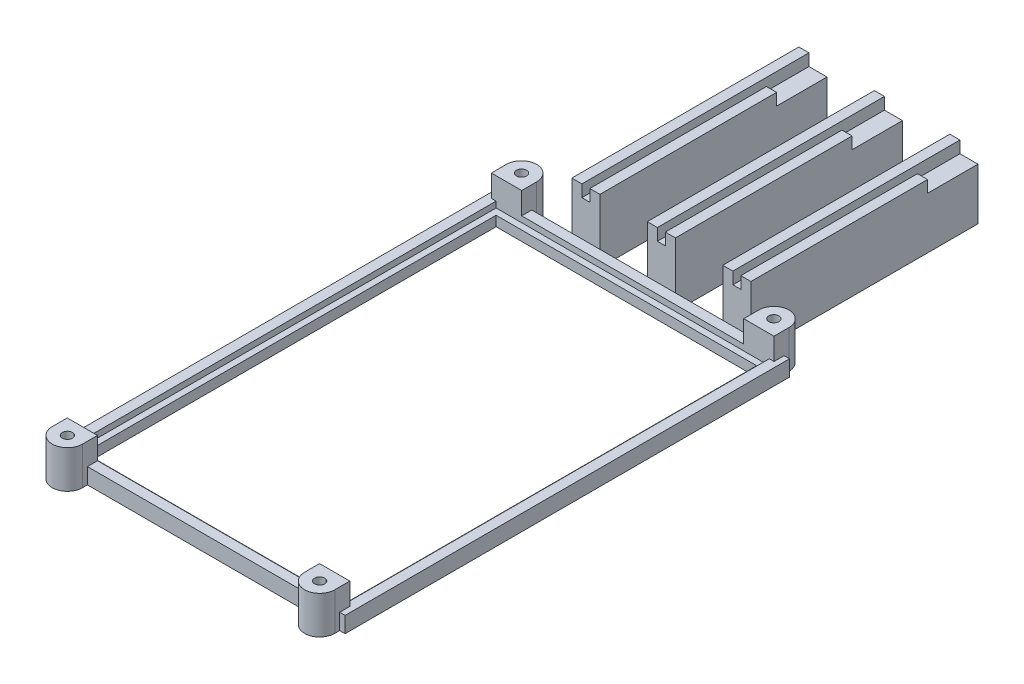
SolidWorks part; units mm, degrees
ref_plane "Front Plane" through (0, 0, 0) normal (0, 0, 1) x (1, 0, 0)
ref_plane "Top Plane" through (0, 0, 0) normal (0, 1, 0) x (1, 0, 0)
ref_plane "Right Plane" through (0, 0, 0) normal (1, 0, 0) x (0, 0, -1)
sketch "Sketch1" plane through (0, 0, 0) normal (0, 1, 0) x (1, 0, 0)
  line L1 (-34.375, -53.375) -> (34.375, -53.375)
  line L2 (-34.375, -53.375) -> (-34.375, 53.375)
  line L3 (-34.375, 53.375) -> (34.375, 53.375)
  line L4 (34.375, -53.375) -> (34.375, 53.375)
  line L5 (-34.375, -53.375) -> (34.375, 53.375) construction
  line L6 (-34.375, 53.375) -> (34.375, -53.375) construction
  point P0 (0, 0)
  dimension "D1" = 68.75
  dimension "D2" = 106.75
extrude "Extrude-Thin1" add sketch "Sketch1" along normal blind 4 thin thin type one direction wall 2.54
sketch "Sketch2" plane through (0, 0, 0) normal (0, 1, 0) x (1, 0, 0)
  line L0 (-34.375, 53.375) -> (0, 19) construction
  line L1 (0, 19) -> (34.375, 53.375) construction
  line L3 (32.7875, -51.7875) -> (-32.7875, -51.7875)
  line L4 (34.375, 53.375) -> (-34.375, 53.375)
  line L5 (34.375, -53.375) -> (34.375, 53.375)
  line L6 (-34.375, -53.375) -> (34.375, -53.375)
  line L7 (-34.375, 53.375) -> (-34.375, -53.375)
  line L8 (34.375, 53.375) -> (-34.375, 53.375)
  line L9 (34.375, -53.375) -> (34.375, 53.375)
  line L10 (-34.375, -53.375) -> (34.375, -53.375)
  line L11 (-34.375, 53.375) -> (-34.375, -53.375)
  line L12 (32.7875, -51.7875) -> (32.7875, 51.7875)
  line L13 (32.7875, 51.7875) -> (-32.7875, 51.7875)
  line L14 (-32.7875, -51.7875) -> (-32.7875, 51.7875)
  line L15 (32.7875, -51.7875) -> (-32.7875, 51.7875) construction
  line L16 (32.7875, 51.7875) -> (-32.7875, -51.7875) construction
  point P2 (0, 0)
  point P11 (-31.0567, 50.0567)
  dimension "D2" = 1.5875
  dimension "D1" = 0
extrude "Boss-Extrude2" add sketch "Sketch2" along normal offset from surface (2.5 mm away) 1.5 up to face at (0, 4, 0)
sketch "Sketch4" plane through (0, 0, -55.915) normal (0, 0, -1) x (-1, 0, 0)
  line L0 (34.375, 4) -> (17.865, 4) construction
  line L1 (-36.915, 4) -> (36.915, 4) construction
  line L2 (17.865, 0) -> (17.865, 16)
  line L3 (-36.915, 0) -> (36.915, 0) construction
  line L4 (17.865, 16) -> (15.325, 16)
  line L5 (15.325, 16) -> (15.325, 13)
  line L6 (15.325, 13) -> (13.325, 13)
  line L7 (13.325, 13) -> (13.325, 16)
  line L8 (13.325, 16) -> (10.785, 16)
  line L9 (10.785, 16) -> (10.785, 0)
  line L10 (10.785, 0) -> (17.865, 0)
  point P9 (22.6104, 16)
  dimension "D1" = 2
  dimension "D2" = 9
  dimension "D3" = 3
  dimension "D4" = 2.54
  dimension "D5" = 19.05
extrude "Boss-Extrude3" add sketch "Sketch4" along normal blind 57.15
sketch "Sketch5" plane through (0, 0, -113.065) normal (0, 0, -1) x (-1, 0, 0)
  line L1 (10.785, 16) -> (13.325, 16)
  line L2 (10.785, 16) -> (10.785, 13)
  line L3 (10.785, 13) -> (13.325, 13)
  line L4 (13.325, 16) -> (13.325, 13)
extrude "Cut-Extrude1" cut sketch "Sketch5" against normal offset from surface (12.7 mm away) 44.45 up to face at (-14.325, 12.25, -55.915)
pattern_linear "LPattern1" count 3 spacing 19 along (1, 0, 0) of "Cut-Extrude1", "Boss-Extrude3"
sketch "Sketch6" plane through (0, 0, 0) normal (0, 1, 0) x (1, 0, 0)
  line L0 (35.56, 57.15) -> (35.56, 53.375)
  line L1 (35.56, 53.375) -> (27.94, 53.375)
  line L2 (34.375, 53.375) -> (-34.375, 53.375) construction
  line L3 (27.94, 53.375) -> (27.94, 57.15)
  circle A0 centre (31.75, 57.15) radius 1.27
  arc A1 (35.56, 57.15) -> (27.94, 57.15) centre (31.75, 57.15) ccw
  dimension "D2" = 2.54
  dimension "D4" = 2.54
  dimension "D1" = 31.75
  dimension "D3" = 57.15
extrude "Boss-Extrude4" add sketch "Sketch6" along normal blind 9.525
mirror "Mirror1" about plane through (0, 0, 0) normal (1, 0, 0) of "Boss-Extrude4"
mirror "Mirror2" about plane through (0, 0, 0) normal (0, 0, 1) of "Mirror1", "Boss-Extrude4"
